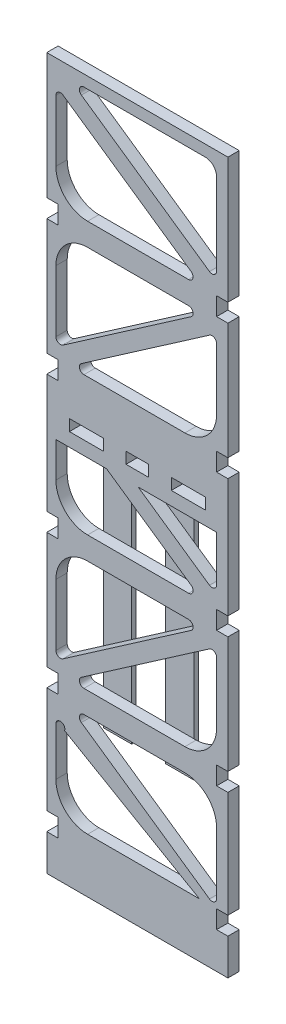
SolidWorks part; units mm, degrees
material "Balsa"
ref_plane "Front Plane" through (0, 0, 0) normal (0, 0, 1) x (1, 0, 0)
ref_plane "Top Plane" through (0, 0, 0) normal (0, 1, 0) x (1, 0, 0)
ref_plane "Right Plane" through (0, 0, 0) normal (1, 0, 0) x (0, 0, -1)
sketch "Model" plane through (0, 0, 0) normal (0, 0, 1) x (1, 0, 0)
  line L0 (77.47, 87.63) -> (20.8312, 87.63)
  line L1 (95.25, 35.3278) -> (95.25, 69.85)
  line L2 (19.3854, 83.0016) -> (91.2642, 33.2394)
  line L3 (5.1107, 145.4001) -> (5.1107, 110.8779)
  line L4 (79.5294, 163.1801) -> (22.8907, 163.1801)
  line L5 (9.0964, 108.7895) -> (80.9752, 158.5518)
  line L6 (77.47, 240.03) -> (20.8312, 240.03)
  line L7 (95.25, 187.7278) -> (95.25, 222.25)
  line L8 (19.3854, 235.4016) -> (91.2642, 185.6394)
  line L9 (22.8907, 175.8801) -> (79.5294, 175.8801)
  line L10 (5.1107, 228.1824) -> (5.1107, 193.6601)
  line L11 (80.9752, 180.5085) -> (9.0964, 230.2708)
  line L12 (91.2642, 154.7206) -> (19.3854, 104.9584)
  line L13 (95.25, 118.11) -> (95.25, 152.6322)
  line L14 (20.8312, 100.33) -> (77.47, 100.33)
  line L15 (5.1107, 297.8001) -> (5.1107, 263.2779)
  line L16 (79.5294, 315.5801) -> (22.8907, 315.5801)
  line L17 (9.0964, 261.1895) -> (80.9752, 310.9518)
  line L18 (88.9, 392.43) -> (20.8312, 392.43)
  line L19 (95.25, 340.1278) -> (95.25, 386.08)
  line L20 (19.3854, 387.8016) -> (91.2642, 338.0394)
  line L21 (22.8907, 328.2801) -> (79.5294, 328.2801)
  line L22 (5.1107, 380.5824) -> (5.1107, 346.0601)
  line L23 (80.9752, 332.9085) -> (9.0964, 382.6708)
  line L24 (22.8907, 30.48) -> (85.6262, 30.48)
  line L25 (5.1107, 75.6336) -> (5.1107, 48.26)
  line L26 (85.6262, 30.48) -> (10.006, 74.3482)
  line L27 (91.2642, 307.1206) -> (19.3854, 257.3584)
  line L28 (95.25, 270.51) -> (95.25, 305.0322)
  line L29 (20.8312, 252.73) -> (77.47, 252.73)
  line L30 (0, 398.78) -> (0, 0)
  line L31 (0, 0) -> (101.6, 0)
  line L32 (101.6, 398.78) -> (101.6, 0)
  line L33 (0, 398.78) -> (101.6, 398.78)
  arc A1 (91.2642, 33.2394) -> (95.25, 35.3278) centre (92.71, 35.3278) ccw
  arc A2 (20.8312, 87.63) -> (19.3854, 83.0016) centre (20.8312, 85.09) ccw
  arc A4 (80.9752, 158.5518) -> (79.5294, 163.1801) centre (79.5294, 160.6401) ccw
  arc A5 (5.1107, 110.8779) -> (9.0964, 108.7895) centre (7.6507, 110.8779) ccw
  arc A7 (91.2642, 185.6394) -> (95.25, 187.7278) centre (92.71, 187.7278) ccw
  arc A8 (20.8312, 240.03) -> (19.3854, 235.4016) centre (20.8312, 237.49) ccw
  arc A10 (9.0964, 230.2708) -> (5.1107, 228.1824) centre (7.6507, 228.1824) ccw
  arc A11 (79.5294, 175.8801) -> (80.9752, 180.5085) centre (79.5294, 178.4201) ccw
  arc A12 (95.25, 152.6322) -> (91.2642, 154.7206) centre (92.71, 152.6322) ccw
  arc A14 (19.3854, 104.9584) -> (20.8312, 100.33) centre (20.8312, 102.87) ccw
  arc A16 (80.9752, 310.9518) -> (79.5294, 315.5801) centre (79.5294, 313.0401) ccw
  arc A17 (5.1107, 263.2779) -> (9.0964, 261.1895) centre (7.6507, 263.2779) ccw
  arc A18 (95.25, 386.08) -> (88.9, 392.43) centre (88.9, 386.08) ccw
  arc A19 (91.2642, 338.0394) -> (95.25, 340.1278) centre (92.71, 340.1278) ccw
  arc A20 (20.8312, 392.43) -> (19.3854, 387.8016) centre (20.8312, 389.89) ccw
  arc A22 (9.0964, 382.6708) -> (5.1107, 380.5824) centre (7.6507, 380.5824) ccw
  arc A23 (79.5294, 328.2801) -> (80.9752, 332.9085) centre (79.5294, 330.8201) ccw
  arc A25 (10.006, 74.3482) -> (5.1107, 75.6336) centre (7.6137, 75.2018) ccw
  arc A27 (95.25, 305.0322) -> (91.2642, 307.1206) centre (92.71, 305.0322) ccw
  arc A29 (19.3854, 257.3584) -> (20.8312, 252.73) centre (20.8312, 255.27) ccw
  arc A30 (5.1107, 48.26) -> (22.8907, 30.48) centre (22.8907, 48.26) ccw
  arc A31 (5.1107, 346.0601) -> (22.8907, 328.2801) centre (22.8907, 346.0601) ccw
  arc A32 (5.1107, 297.8001) -> (22.8907, 315.5801) centre (22.8907, 297.8001) cw
  arc A33 (95.25, 270.51) -> (77.47, 252.73) centre (77.47, 270.51) cw
  arc A34 (77.47, 240.03) -> (95.25, 222.25) centre (77.47, 222.25) cw
  arc A35 (5.1107, 193.6601) -> (22.8907, 175.8801) centre (22.8907, 193.6601) ccw
  arc A36 (5.1107, 145.4001) -> (22.8907, 163.1801) centre (22.8907, 145.4001) cw
  arc A37 (77.47, 100.33) -> (95.25, 118.11) centre (77.47, 118.11) ccw
  arc A38 (77.47, 87.63) -> (95.25, 69.85) centre (77.47, 69.85) cw
  dimension "D3" = 6.35
  dimension "D4" = 2.54
  dimension "D5" = 2.54
  dimension "D6" = 2.54
  dimension "D7" = 2.54
  dimension "D8" = 2.54
  dimension "D9" = 2.54
  dimension "D10" = 2.54
  dimension "D11" = 2.54
  dimension "D12" = 2.54
  dimension "D13" = 2.54
  dimension "D14" = 2.54
  dimension "D15" = 2.54
  dimension "D16" = 2.54
  dimension "D17" = 2.54
  dimension "D18" = 2.54
  dimension "D19" = 2.54
  dimension "D20" = 2.54
  dimension "D21" = 2.54
  dimension "D26" = 17.78
  dimension "D27" = 17.78
  dimension "D1" = 398.78
  dimension "D2" = 101.6
  dimension "D25" = 87.4233
  dimension "D28" = 30.48
extrude "Boss-Extrude1" add sketch "Model" along normal blind 6.35
sketch "Sketch1" plane through (0, 0, 6.35) normal (0, 0, 1) x (1, 0, 0)
  line L0 (101.6, 0) -> (101.6, 398.78) construction
  line L1 (101.6, 328.2801) -> (95.25, 328.2801)
  line L2 (101.6, 328.2801) -> (101.6, 318.1201)
  line L3 (101.6, 318.1201) -> (95.25, 318.1201)
  line L4 (95.25, 328.2801) -> (95.25, 318.1201)
  line L5 (0, 398.78) -> (0, 0) construction
  line L6 (0, 252.73) -> (6.35, 252.73)
  line L7 (0, 252.73) -> (0, 242.57)
  line L8 (0, 242.57) -> (6.35, 242.57)
  line L9 (6.35, 252.73) -> (6.35, 242.57)
  line L10 (22.8907, 328.2801) -> (79.5294, 328.2801) construction
  line L11 (101.6, 175.8801) -> (95.25, 175.8801)
  line L12 (101.6, 175.8801) -> (101.6, 165.7201)
  line L13 (101.6, 165.7201) -> (95.25, 165.7201)
  line L14 (95.25, 175.8801) -> (95.25, 165.7201)
  line L15 (0, 100.33) -> (6.35, 100.33)
  line L16 (0, 100.33) -> (0, 90.17)
  line L17 (0, 90.17) -> (6.35, 90.17)
  line L18 (6.35, 100.33) -> (6.35, 90.17)
  line L19 (20.8312, 252.73) -> (77.47, 252.73) construction
  line L21 (20.8312, 100.33) -> (77.47, 100.33) construction
  line L22 (22.8907, 30.48) -> (85.6262, 30.48) construction
  line L23 (0, 328.2801) -> (6.35, 328.2801)
  line L24 (0, 328.2801) -> (0, 318.1201)
  line L25 (0, 318.1201) -> (6.35, 318.1201)
  line L26 (6.35, 328.2801) -> (6.35, 318.1201)
  line L27 (101.6, 252.73) -> (95.25, 252.73)
  line L28 (101.6, 252.73) -> (101.6, 242.57)
  line L29 (101.6, 242.57) -> (95.25, 242.57)
  line L30 (95.25, 252.73) -> (95.25, 242.57)
  line L31 (0, 175.8801) -> (6.35, 175.8801)
  line L32 (0, 175.8801) -> (0, 165.7201)
  line L33 (0, 165.7201) -> (6.35, 165.7201)
  line L34 (6.35, 175.8801) -> (6.35, 165.7201)
  line L35 (101.6, 100.33) -> (95.25, 100.33)
  line L36 (101.6, 100.33) -> (101.6, 90.17)
  line L37 (101.6, 90.17) -> (95.25, 90.17)
  line L38 (95.25, 100.33) -> (95.25, 90.17)
  line L39 (0, 30.48) -> (6.35, 30.48)
  line L40 (0, 30.48) -> (0, 20.32)
  line L41 (0, 20.32) -> (6.35, 20.32)
  line L42 (6.35, 30.48) -> (6.35, 20.32)
  line L43 (101.6, 30.48) -> (95.25, 30.48)
  line L44 (101.6, 30.48) -> (101.6, 20.32)
  line L45 (101.6, 20.32) -> (95.25, 20.32)
  line L46 (95.25, 30.48) -> (95.25, 20.32)
  line L47 (22.8907, 175.8801) -> (79.5294, 175.8801) construction
  dimension "D1" = 6.35
  dimension "D2" = 10.16
  dimension "D3" = 10.16
  dimension "D4" = 6.35
  dimension "D5" = 6.35
  dimension "D6" = 10.16
  dimension "D7" = 6.35
  dimension "D8" = 10.16
  dimension "D9" = 10.16
  dimension "D10" = 10.16
extrude "Cut-Extrude1" cut sketch "Sketch1" against normal up to surface (6.35 mm away) contours L1 L4 L3 L2 | L27 L30 L29 L28 | L9 L6 L7 L8 | L42 L39 L40 L41 | L11 L14 L13 L12 | L26 L25 L24 L23 | L43 L46 L45 L44 | L38 L37 L36 L35 | L15 L18 L17 L16 | L31 L34 L33 L32 region at (98.425, 323.2001, 6.35) region at (3.175, 247.65, 6.35) region at (98.425, 170.8001, 6.35) region at (98.425, 247.65, 6.35) region at (3.175, 25.4, 6.35) up to face at (50.8, 199.39, 0)
sketch "Sketch2" plane through (0, 0, 6.35) normal (0, 0, 1) x (1, 0, 0)
  line L0 (77.47, 240.03) -> (20.8312, 240.03) construction
  line L1 (1.7778, 240.03) -> (97.5543, 240.03)
  line L2 (1.7778, 240.03) -> (1.7778, 213.36)
  line L3 (1.7778, 213.36) -> (97.5543, 213.36)
  line L4 (97.5543, 240.03) -> (97.5543, 213.36)
  dimension "D1" = 26.67
extrude "Boss-Extrude2" add sketch "Sketch2" against normal up to surface (6.35 mm away) up to face at (50.8, 174.9082, 0)
sketch "Sketch3" plane through (0, 0, 6.35) normal (0, 0, 1) x (1, 0, 0)
  line L1 (88.9, 227.33) -> (69.85, 227.33)
  line L2 (88.9, 227.33) -> (88.9, 220.98)
  line L3 (88.9, 220.98) -> (69.85, 220.98)
  line L4 (69.85, 227.33) -> (69.85, 220.98)
  line L5 (101.6, 175.8801) -> (101.6, 242.57) construction
  line L6 (0, 242.57) -> (0, 175.8801) construction
  line L7 (31.75, 220.98) -> (12.7, 220.98)
  line L8 (31.75, 220.98) -> (31.75, 227.33)
  line L9 (31.75, 227.33) -> (12.7, 227.33)
  line L10 (12.7, 220.98) -> (12.7, 227.33)
  line L12 (5.1107, 213.36) -> (33.5231, 213.36) construction
  line L13 (57.15, 220.98) -> (44.45, 220.98)
  line L14 (57.15, 220.98) -> (57.15, 227.33)
  line L15 (57.15, 227.33) -> (44.45, 227.33)
  line L16 (44.45, 220.98) -> (44.45, 227.33)
  line L17 (51.2233, 213.36) -> (95.25, 213.36) construction
  dimension "D2" = 6.35
  dimension "D3" = 12.7
  dimension "D4" = 19.05
  dimension "D5" = 12.7
  dimension "D6" = 19.05
  dimension "D7" = 6.35
  dimension "D8" = 7.62
  dimension "D9" = 12.7
  dimension "D10" = 12.7
  dimension "D11" = 7.62
extrude "Cut-Extrude2" cut sketch "Sketch3" against normal up to surface (6.35 mm away) up to face at (83.4048, 199.7204, 0)
sketch "Sketch4" plane through (0, 0, 0) normal (0, 0, -1) x (-1, 0, 0)
  line L0 (-25.4, 207.264) -> (-25.4, 80.264) construction
  line L1 (-25.4, 80.264) -> (-41.275, 80.264) construction
  line L2 (-41.275, 80.264) -> (-41.275, 207.264) construction
  line L3 (-41.275, 207.264) -> (-25.4, 207.264) construction
  line L4 (-60.325, 207.264) -> (-60.325, 80.264) construction
  line L5 (-60.325, 80.264) -> (-76.2, 80.264) construction
  line L6 (-76.2, 80.264) -> (-76.2, 207.264) construction
  line L7 (-76.2, 207.264) -> (-60.325, 207.264) construction
  line L8 (-25.4, 207.264) -> (-25.4, 80.264)
  line L9 (-25.4, 80.264) -> (-41.275, 80.264)
  line L10 (-41.275, 80.264) -> (-41.275, 207.264)
  line L11 (-41.275, 207.264) -> (-25.4, 207.264)
  line L12 (-60.325, 207.264) -> (-60.325, 80.264)
  line L13 (-60.325, 80.264) -> (-76.2, 80.264)
  line L14 (-76.2, 80.264) -> (-76.2, 207.264)
  line L15 (-76.2, 207.264) -> (-60.325, 207.264)
extrude "Boss-Extrude3" add sketch "Sketch4" along normal blind 2.54 separate body
equation "\"thick\"=0.25"
equation "\"D1@Boss-Extrude1\"=\"thick\""
